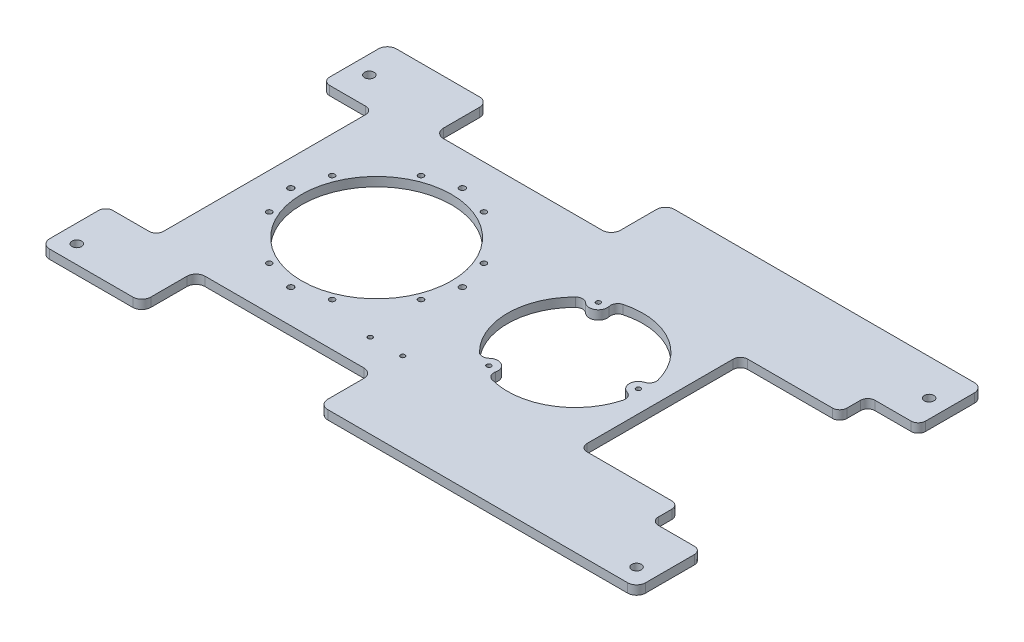
SolidWorks part; units mm, degrees
material "6061 Alloy"
ref_plane "Front Plane" through (0, 0, 0) normal (0, 0, 1) x (1, 0, 0)
ref_plane "Top Plane" through (0, 0, 0) normal (0, 1, 0) x (1, 0, 0)
ref_plane "Right Plane" through (0, 0, 0) normal (1, 0, 0) x (0, 0, -1)
sketch "Sketch1" plane through (0, 0, 0) normal (0, 1, 0) x (1, 0, 0)
  line L1 (0, 0) -> (330, 0)
  line L2 (0, 0) -> (0, 192)
  line L3 (0, 192) -> (330, 192)
  line L4 (330, 0) -> (330, 192)
  dimension "D1" = 192
  dimension "D2" = 330
extrude "Boss-Extrude1" add sketch "Sketch1" along normal blind 5
sketch "Sketch2" plane through (0, 5, 0) normal (0, 1, 0) x (1, 0, 0)
  line L0 (0, 0) -> (330, 0) construction
  line L1 (0, 0) -> (0, 192)
  line L2 (135.5, 96) -> (90, 96) construction
  line L3 (90, 96) -> (0, 96) construction
  line L4 (132.0365, 113.4121) -> (90, 96) construction
  circle A0 centre (90, 96) radius 50 construction
  circle A1 centre (90, 96) radius 45.5 construction
  circle A10 centre (132.0365, 113.4121) radius 1.5
  circle A11 centre (132.0365, 78.5879) radius 1.5
  circle A12 centre (107.4121, 53.9635) radius 1.5
  circle A13 centre (72.5879, 53.9635) radius 1.5
  circle A14 centre (47.9635, 78.5879) radius 1.5
  circle A15 centre (47.9635, 113.4121) radius 1.5
  circle A16 centre (72.5879, 138.0365) radius 1.5
  circle A17 centre (107.4121, 138.0365) radius 1.5
  point P21 (90, 96)
  point P30 (90, 96)
  dimension "D1" = 100
  dimension "D2" = 91
  dimension "D3" = 22.5
  dimension "D8" = 8
  dimension "D4" = 3
  dimension "D5" = 192
  dimension "D6" = 330
  dimension "D7" = 90
extrude "Cut-Extrude1" cut sketch "Sketch2" against normal through all and the other way through all contours A16 | A17 | A10 | A11 | A12 | A13 | A14 | A15
sketch "Sketch3" plane through (0, 5, 0) normal (0, 1, 0) x (1, 0, 0)
  line L0 (0, 0) -> (0, 192)
  line L1 (0, 0) -> (330, 0)
  line L2 (0, 0) -> (330, 0) construction
  circle A0 centre (90, 96) radius 41.5
  circle A1 centre (90, 96) radius 44 construction
  circle A5 centre (47.9635, 113.4121) radius 1.5 construction
  circle A6 centre (72.5879, 53.9635) radius 1.5 construction
  circle A7 centre (132.0365, 113.4121) radius 1.5 construction
  dimension "D1" = 83
  dimension "D2" = 330
  dimension "D3" = 192
extrude "Cut-Extrude2" cut sketch "Sketch3" against normal through all contours A0 region at (90, 5, -96)
hole_wizard "M5 Clearance Hole1" positions "Sketch13" profile "Sketch14" hole size "M5" standard "DIN"
sketch "Sketch13" plane through (0, 5, 0) normal (0, 1, 0) x (1, 0, 0)
  line L0 (0, 192) -> (0, 0) construction
  line L1 (330, 0) -> (330, 192) construction
  line L2 (10, 172) -> (320, 172) construction
  line L3 (320, 172) -> (320, 10) construction
  line L4 (320, 10) -> (10, 10) construction
  line L5 (10, 10) -> (10, 172) construction
  line L15 (330, 192) -> (0, 192) construction
  point P0 (10, 172)
  point P2 (10, 10)
  point P4 (320, 10)
  point P6 (320, 172)
  dimension "D1" = 10
  dimension "D2" = 10
  dimension "D3" = 10
  dimension "D4" = 10
  dimension "D5" = 162
  dimension "D6" = 162
  dimension "D7" = 20
sketch "Sketch14" plane through (10, 5, -172) normal (1, 0, 0) x (0, 0, 1)
  line L0 (0, 0) -> (0, 13.5323)
  line L1 (0, 13.5323) -> (2.65, 11.94)
  line L2 (2.65, 11.94) -> (2.65, 0)
  line L5 (2.65, 0) -> (0, 0)
  line L10 (0, 13.5323) -> (-2.65, 11.94) construction
  line L11 (0, -6.35) -> (0, 107.95) construction
  dimension "Hole Dia." = 5.3
  dimension "Hole Depth" = 11.94
  dimension "Drill Angle" = 118
hole_wizard "Tap Drill for M4 Tap1" positions "Sketch17" profile "Sketch18" hole size "M4" standard "DIN" end condition through all
sketch "Sketch17" plane through (0, 5, 0) normal (0, 1, 0) x (1, 0, 0)
  line L0 (132.0365, 113.4121) -> (132.0365, 78.5879)
  line L2 (132.0365, 96) -> (137.5, 96)
  line L3 (42.5, 96) -> (137.5, 96) construction
  circle A0 centre (90, 96) radius 47.5
  circle A1 centre (90, 96) radius 41.5 construction
  circle A3 centre (90, 96) radius 47.5 construction
  circle A6 centre (132.0365, 78.5879) radius 1.5 construction
  circle A7 centre (132.0365, 113.4121) radius 1.5 construction
  point P0 (137.5, 96)
  point P22 (90, 48.5)
  point P23 (42.5, 96)
  point P24 (90, 143.5)
  dimension "D1" = 95
  dimension "D2" = 4
sketch "Sketch18" plane through (137.5, 5, -96) normal (1, 0, 0) x (0, 0, 1)
  line L0 (0, 0) -> (0, 5)
  line L1 (0, 5) -> (1.65, 5)
  line L2 (1.65, 5) -> (1.65, 0)
  line L5 (1.65, 0) -> (0, 0)
  line L11 (0, -6.35) -> (0, 107.95) construction
  dimension "Thru Hole Dia." = 3.3
  dimension "Thru Hole Depth" = 5
sketch "Sketch19" plane through (0, 5, 0) normal (0, 1, 0) x (1, 0, 0)
  line L0 (0, 192) -> (0, 0) construction
  line L1 (0, 156) -> (28, 156)
  line L2 (0, 156) -> (0, 36)
  line L3 (0, 36) -> (28, 36)
  line L4 (28, 156) -> (28, 36)
  line L5 (330, 0) -> (330, 192) construction
  line L6 (330, 156) -> (302, 156)
  line L7 (330, 156) -> (330, 36)
  line L8 (330, 36) -> (302, 36)
  line L9 (302, 156) -> (302, 36)
  line L10 (0, 96) -> (28, 96) construction
  dimension "D1" = 120
  dimension "D2" = 28
extrude "Cut-Extrude3" cut sketch "Sketch19" against normal through all and the other way through all
sketch "Sketch21" plane through (0, 0, 0) normal (0, -1, 0) x (1, 0, 0)
  line L1 (302, -51.5) -> (247, -51.5)
  line L2 (302, -51.5) -> (302, -140.5)
  line L3 (302, -140.5) -> (247, -140.5)
  line L4 (247, -51.5) -> (247, -140.5)
  line L5 (302, -96) -> (302, -156) construction
  line L6 (302, -96) -> (302, -36) construction
  circle A0 centre (190.7932, -95.584) radius 40 construction
  dimension "D3" = 80
  dimension "D1" = 55
  dimension "D2" = 89
extrude "Cut-Extrude4" cut sketch "Sketch21" against normal through all
fillet "Fillet1" radius 4 12 edges at (330, 2.5, -36) (302, 2.5, -36) (330, 2.5, -156) (302, 2.5, -156) (28, 2.5, -156) (28, 2.5, -36) (0, 2.5, -36) (0, 2.5, -156) (247, 2.5, -51.5) (247, 2.5, -140.5) (302, 2.5, -140.5) (302, 2.5, -51.5)
sketch "Sketch23" plane through (0, 0, 0) normal (0, 0, 1) x (1, 0, 0)
  line L0 (131.5, 5) -> (48.5, 5) construction
  line L1 (131.5, 5) -> (48.5, 5)
  point P2 (165, 3)
  point P3 (90, 5)
ref_axis "Axis1" through (90, 5, 0) along (0, 0, -1)
sketch "Sketch24" plane through (247, 0, 0) normal (1, 0, 0) x (0, 0, -1)
  line L0 (137.5, 5) -> (54.5, 5) construction
  line L1 (137.5, 5) -> (54.5, 5)
  point P2 (96, 3)
ref_axis "Axis2" through (247, 3, -96) along (-1, 0, 0)
hole_wizard "Tap Drill for M3 Tap1" positions "Sketch25" profile "Sketch26" hole size "M3" standard "DIN" end condition up to next
sketch "Sketch25" plane through (0, 0, 0) normal (0, -1, 0) x (-1, 0, 0)
  line L0 (-247, 96) -> (-210.0032, 96) construction
  line L1 (-182.5, 126.3109) -> (-182.5, 65.6891) construction
  circle A0 centre (-200, 96) radius 35 construction
  circle A1 centre (-90, 96) radius 41.5 construction
  point P6 (-182.5, 65.6891)
  point P14 (-235, 96)
  point P15 (-182.5, 126.3109)
  dimension "D1" = 70
  dimension "D3" = 110
  dimension "D2" = 3
sketch "Sketch26" plane through (182.5, 0, -126.3109) normal (1, 0, 0) x (0, 0, -1)
  line L0 (0, 0) -> (0, 5)
  line L1 (0, 5) -> (1.25, 5)
  line L2 (1.25, 5) -> (1.25, 0)
  line L5 (1.25, 0) -> (0, 0)
  line L11 (0, -6.35) -> (0, 107.95) construction
  dimension "Thru Hole Dia." = 2.5
  dimension "Thru Hole Depth" = 5
sketch "Sketch29" plane through (0, 0, 0) normal (0, -1, 0) x (1, 0, 0)
  line L0 (200, -67.5) -> (90, -67.5)
  line L1 (145, -67.5) -> (145, -24.0733)
hole_wizard "Tap Drill for M3 Tap2" positions "Sketch30" profile "Sketch31" hole size "M3" standard "DIN" end condition up to next
sketch "Sketch30" plane through (0, 0, 0) normal (0, -1, 0) x (-1, 0, 0)
  point P0 (-154, 46.5)
  point P3 (-136, 46.5)
  dimension "D1" = 18
  dimension "D2" = 9
  dimension "D3" = 21
sketch "Sketch31" plane through (154, 0, -46.5) normal (1, 0, 0) x (0, 0, -1)
  line L0 (0, 0) -> (0, 5)
  line L1 (0, 5) -> (1.25, 5)
  line L2 (1.25, 5) -> (1.25, 0)
  line L5 (1.25, 0) -> (0, 0)
  line L11 (0, -6.35) -> (0, 107.95) construction
  dimension "Thru Hole Dia." = 2.5
  dimension "Thru Hole Depth" = 5
sketch "Sketch32" plane through (0, 0, 0) normal (0, -1, 0) x (1, 0, 0)
  circle A0 centre (200, -96) radius 35 construction
  circle A1 centre (200, -96) radius 37.5
  circle A2 centre (182.5, -65.6891) radius 5
  circle A3 centre (182.5, -126.3109) radius 5
  circle A4 centre (235, -96) radius 5
  point P0 (182.5, -65.6891)
  point P1 (182.5, -126.3109)
  point P2 (235, -96)
  dimension "D1" = 75
  dimension "D2" = 10
extrude "Cut-Extrude5" cut sketch "Sketch32" against normal through all contours A4 A1 A2 A3 region at (200, 0, -96)
fillet "Fillet2" radius 4 6 edges at (237.2321, 2.5, -91.5259) (237.2321, 2.5, -100.4741) (177.5092, 2.5, -126.0069) (185.2586, 2.5, -130.481) (185.2586, 2.5, -61.519) (177.5092, 2.5, -65.9931)
sketch "Sketch33" plane through (0, 0, 0) normal (0, -1, 0) x (1, 0, 0)
  line L0 (56, 0) -> (56, -40) construction
  line L1 (0, 0) -> (56, 0) construction
  line L2 (0, 0) -> (0, -40) construction
  line L3 (0, -40) -> (56, -40) construction
  line L4 (28, 0) -> (28, -40) construction
  line L5 (330, 0) -> (164, 0) construction
  line L6 (330, 0) -> (330, -55.5) construction
  line L7 (330, -55.5) -> (164, -55.5) construction
  line L8 (247, 0) -> (247, -55.5) construction
  line L9 (164, 0) -> (164, -55.5) construction
  line L11 (56, 0) -> (154, 0)
  line L12 (56, 0) -> (56, -30)
  line L13 (56, -30) -> (154, -30)
  line L14 (154, 0) -> (154, -30)
  line L15 (28, -96) -> (85.3759, -96) construction
  line L16 (28, -40) -> (28, -152) construction
  line L17 (56, -162) -> (154, -162)
  line L18 (154, -192) -> (154, -162)
  line L19 (56, -192) -> (154, -192)
  line L20 (56, -192) -> (56, -162)
  dimension "D1" = 30
extrude "Cut-Extrude6" cut sketch "Sketch33" against normal through all
fillet "Fillet3" radius 5 12 edges at (154, 2.5, -192) (154, 2.5, -162) (56, 2.5, -162) (56, 2.5, -192) (154, 2.5, 0) (154, 2.5, -30) (56, 2.5, 0) (56, 2.5, -30) (330, 2.5, -192) (330, 2.5, 0) (0, 2.5, 0) (0, 2.5, -192)
equation "\"D2@Sketch13\"=\"D1@Sketch13\""
equation "\"D3@Sketch13\"=\"D1@Sketch13\""
equation "\"D4@Sketch13\"=\"D1@Sketch13\""
equation "\"D6@Sketch13\"=\"D5@Sketch13\""
